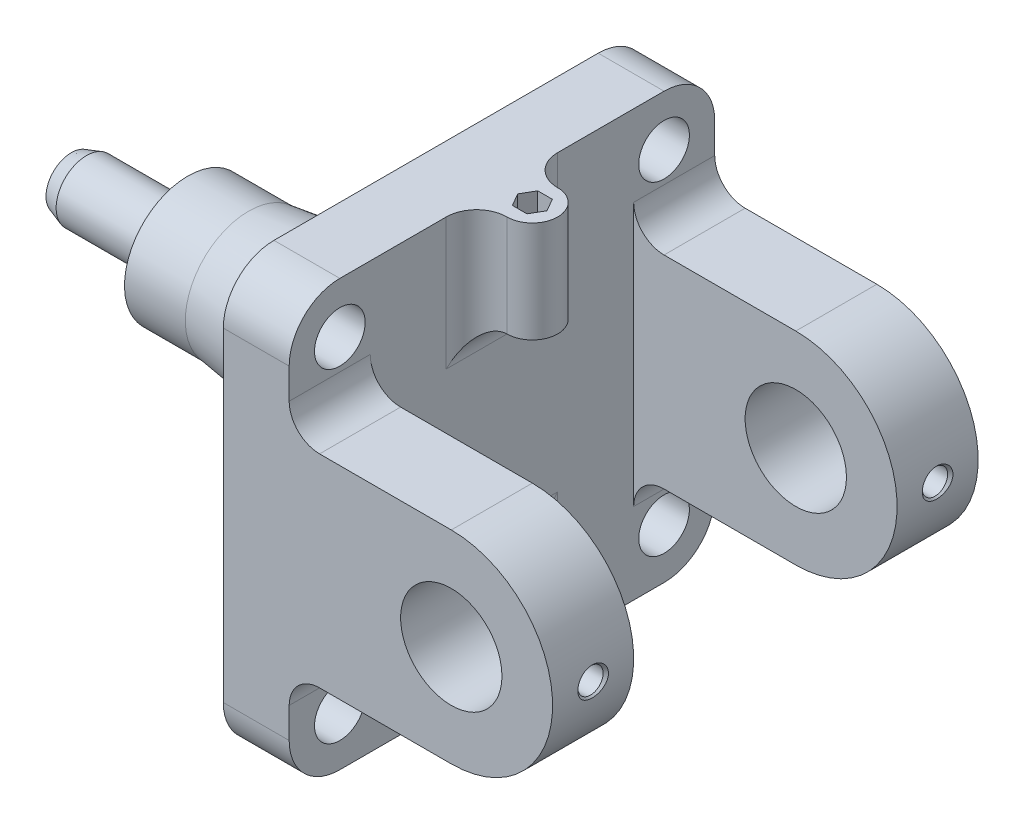
SolidWorks part; units mm, degrees
ref_plane "Front Plane" through (0, 0, 0) normal (0, 0, 1) x (1, 0, 0)
ref_plane "Top Plane" through (0, 0, 0) normal (0, 1, 0) x (1, 0, 0)
ref_plane "Right Plane" through (0, 0, 0) normal (1, 0, 0) x (0, 0, -1)
sketch "Esquisse1" plane through (0, 0, 0) normal (1, 0, 0) x (0, 0, -1)
  line L0 (-32, -32) -> (32, -32) construction
  line L2 (-32, -42) -> (32, -42)
  line L3 (32, -32) -> (32, 32) construction
  line L5 (42, -32) -> (42, 32)
  line L6 (-32, -32) -> (32, 32) construction
  line L9 (-32, 42) -> (32, 42)
  line L10 (-42, -32) -> (-42, 32)
  arc A2 (32, -42) -> (42, -32) centre (32, -32) ccw
  arc A4 (-32, -42) -> (-42, -32) centre (-32, -32) cw
  arc A5 (32, 42) -> (42, 32) centre (32, 32) cw
  arc A6 (-42, 32) -> (-32, 42) centre (-32, 32) cw
  point P2 (-35.241, -32.4067)
  point P3 (0, 0)
  point P9 (1.759, 4.5933)
  dimension "D3" = 10
  dimension "D1" = 64
  dimension "D2" = 64
extrude "Boss.-Extru.1" add sketch "Esquisse1" along normal blind 13
sketch "Esquisse2" plane through (0, 0, 0) normal (0, 0, 1) x (1, 0, 0)
  line L0 (-37, 12.5) -> (-12, 16)
  line L1 (0, 0) -> (-12, 0)
  line L2 (0, 0) -> (0, 16)
  line L3 (0, 16) -> (-12, 16)
  line L5 (-12, 0) -> (-37, 0)
  line L9 (-72, 5) -> (-69, 6)
  line L10 (-37, 12.5) -> (-49, 12.5)
  line L12 (-37, 0) -> (-49, 0)
  line L13 (-49, 12.5) -> (-49, 6)
  line L14 (-49, 0) -> (-69, 0)
  line L16 (-49, 6) -> (-69, 6)
  line L18 (-69, 0) -> (-72, 0)
  line L21 (-72, 0) -> (-72, 5)
  dimension "D1" = 16
  dimension "D2" = 12
  dimension "D3" = 12.5
  dimension "D4" = 25
  dimension "D5" = 12
  dimension "D6" = 20
  dimension "D7" = 6
  dimension "D8" = 3
  dimension "D9" = 5
revolve "Révolution1" add sketch "Esquisse2" angle 360 about L1
sketch "Esquisse3" plane through (13, 0, 0) normal (1, 0, 0) x (0, 0, -1)
  line L0 (-32, 32) -> (32, 32) construction
  line L1 (0, 0) -> (28.1484, 0) construction
  line L2 (0, 0) -> (0, 44.4192) construction
  circle A0 centre (-32, 32) radius 5
  circle A1 centre (32, 32) radius 5
  circle A2 centre (-32, -32) radius 5
  circle A3 centre (32, -32) radius 5
  point P7 (0, 32)
  dimension "D1" = 10
  dimension "D2" = 64
  dimension "D3" = 32
extrude "Enlèv. mat.-Extru.1" cut sketch "Esquisse3" against normal blind 13
sketch "Esquisse4" plane through (0, 0, 42) normal (0, 0, 1) x (1, 0, 0)
  line L0 (0, 0) -> (45, 0) construction
  line L1 (13, 20) -> (45, 20)
  line L2 (13, -20) -> (45, -20)
  line L3 (13, 32) -> (13, -32) construction
  line L4 (13, 20) -> (13, -20)
  arc A1 (45, -20) -> (45, 20) centre (45, 0) ccw
  circle A2 centre (45, 0) radius 10
  point P3 (22.5, 0)
  dimension "D1" = 20
  dimension "D3" = 20
  dimension "D2" = 45
extrude "Boss.-Extru.2" add sketch "Esquisse4" against normal blind 16
mirror "Symétrie3" about plane through (0, 0, 0) normal (0, 0, 1) of "Boss.-Extru.2"
sketch "Esquisse5" plane through (0, -42, 0) normal (0, -1, 0) x (1, 0, 0)
  line L0 (0, 0) -> (19, 0) construction
  line L1 (13, 5) -> (19, 5)
  line L2 (13, -5) -> (19, -5)
  line L3 (13, 32) -> (13, -32) construction
  line L4 (21.8868, 0) -> (20.4434, 2.5)
  line L5 (20.4434, 2.5) -> (17.5566, 2.5)
  line L6 (17.5566, 2.5) -> (16.1132, 0)
  line L7 (16.1132, 0) -> (17.5566, -2.5)
  line L8 (17.5566, -2.5) -> (20.4434, -2.5)
  line L9 (20.4434, -2.5) -> (21.8868, 0)
  line L10 (13, 5) -> (13, -5)
  arc A1 (19, -5) -> (19, 5) centre (19, 0) ccw
  circle A2 centre (19, 0) radius 2.5 construction
  point P3 (9.5, 0)
  dimension "D2" = 5
  dimension "D1" = 10
  dimension "D3" = 19
extrude "Boss.-Extru.3" add sketch "Esquisse5" against normal blind 20
mirror "Symétrie4" about plane through (0, 0, 0) normal (0, 1, 0) of "Boss.-Extru.3"
fillet "Congé1" radius 6 4 edges at (13, -20, 34) (13, -20, -34) (13, 20, 34) (13, 20, -34)
fillet "Congé2" radius 6 4 edges at (13, -32, -5) (13, 32, -5) (13, 32, 5) (13, -32, 5)
fillet "Congé3" radius 6 2 edges at (13, 22, 0) (13, -22, 0)
ref_plane "Plan1" through (65, 0, 0) normal (1, 0, 0) x (0, 0, -1)
hole_wizard "Trou taraudé M61" positions "Esquisse7" profile "Esquisse8" tap size "M6" standard "ISO" end condition up to next
sketch "Esquisse7" plane through (65, 0, 0) normal (1, 0, 0) x (0, 0, -1)
  line L0 (-42, 20) -> (-42, -20) construction
  line L1 (42, -20) -> (42, 20) construction
  point P0 (-34, 0)
  point P2 (34, 0)
  point P6 (-42, 0)
  dimension "D1" = 8
  dimension "D2" = 8
sketch "Esquisse8" plane through (65, 0, 34) normal (0, 1, 0) x (0, 0, -1)
  line L0 (0, 0) -> (0, 10)
  line L1 (0, 10) -> (2.5, 10)
  line L2 (2.5, 10) -> (2.5, 0.525)
  line L3 (2.5, 0.525) -> (3.025, 0)
  line L5 (3.025, 0) -> (0, 0)
  line L6 (-2.5, 0.525) -> (-3.025, 0) construction
  line L11 (0, -6.35) -> (0, 107.95) construction
  dimension "Diamètre du trou pour taraudage jusqu'au prochain" = 5
  dimension "Profondeur du trou pour taraudage jusqu'au prochain" = 10
  dimension "Diamètre du fraisage entrant" = 6.05
  dimension "Angle du fraisage entrant" = 90
